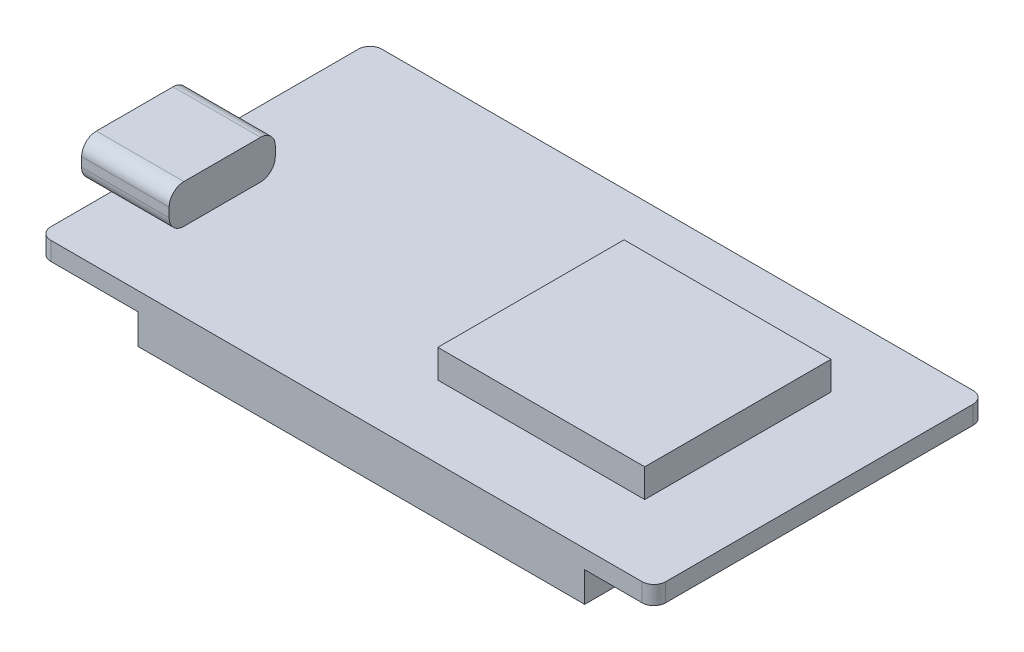
SolidWorks part; units mm, degrees
ref_plane "前基準面" through (0, 0, 0) normal (0, 0, 1) x (1, 0, 0)
ref_plane "上基準面" through (0, 0, 0) normal (0, 1, 0) x (1, 0, 0)
ref_plane "右基準面" through (0, 0, 0) normal (1, 0, 0) x (0, 0, -1)
sketch "草圖1" plane through (0, 0, 0) normal (0, 1, 0) x (1, 0, 0)
  line L1 (-26, 14) -> (26, 14)
  line L2 (-26, 14) -> (-26, -14)
  line L3 (-26, -14) -> (26, -14)
  line L4 (26, 14) -> (26, -14)
  line L5 (-26, 14) -> (26, -14) construction
  line L6 (-26, -14) -> (26, 14) construction
  point P0 (0, 0)
  dimension "D1" = 28
  dimension "D2" = 52
extrude "填料-伸長1" add sketch "草圖1" along normal blind 1.55
fillet "圓角1" radius 1 4 edges at (26, 0.775, -14) (-26, 0.775, -14) (-26, 0.775, 14) (26, 0.775, 14)
sketch "草圖2" plane through (0, 0, 0) normal (0, -1, 0) x (1, 0, 0)
  line L0 (-25, 14) -> (25, 14) construction
  line L1 (-17.61, 14) -> (20.15, 14)
  line L2 (-17.61, 14) -> (-17.61, 11.46)
  line L3 (-17.61, 11.46) -> (20.15, 11.46)
  line L4 (20.15, 14) -> (20.15, 11.46)
  line L5 (26, 13) -> (26, -13) construction
  line L6 (-26, 0) -> (26, 0) construction
  line L7 (-26, -13) -> (-26, 13) construction
  line L8 (20.15, -14) -> (20.15, -11.46)
  line L9 (-17.61, -14) -> (-17.61, -11.46)
  line L10 (-17.61, -14) -> (20.15, -14)
  line L11 (-17.61, -11.46) -> (20.15, -11.46)
  dimension "D1" = 2.54
  dimension "D2" = 37.76
  dimension "D3" = 5.85
extrude "填料-伸長2" add sketch "草圖2" along normal blind 2.54
sketch "草圖3" plane through (0, 1.55, 0) normal (0, 1, 0) x (1, 0, 0)
  line L0 (26, -13) -> (26, 13) construction
  line L1 (1.6, 7.875) -> (19.1, 7.875)
  line L2 (1.6, 7.875) -> (1.6, -7.875)
  line L3 (1.6, -7.875) -> (19.1, -7.875)
  line L4 (19.1, 7.875) -> (19.1, -7.875)
  line L5 (1.6, 7.875) -> (19.1, -7.875) construction
  line L6 (1.6, -7.875) -> (19.1, 7.875) construction
  point P0 (10.35, 0)
  dimension "D1" = 17.5
  dimension "D2" = 15.75
  dimension "D3" = 6.9
extrude "填料-伸長4" add sketch "草圖3" along normal blind 2.4
sketch "草圖5" plane through (-26, 0, 0) normal (-1, 0, 0) x (0, 0, 1)
  line L0 (-13, 1.55) -> (13, 1.55) construction
  line L1 (7.35, 1.55) -> (0.87, 1.55)
  line L2 (8.6, 2.8) -> (8.6, 3.58)
  line L3 (7.35, 4.83) -> (0.87, 4.83)
  line L4 (-0.38, 2.8) -> (-0.38, 3.58)
  line L5 (-7.875, 1.55) -> (7.875, 1.55) construction
  line L6 (14, 1.55) -> (14, 0) construction
  line L7 (-0.38, 3.19) -> (8.6, 3.19) construction
  line L8 (4.11, 4.83) -> (4.11, 1.55) construction
  arc A0 (0.87, 4.83) -> (-0.38, 3.58) centre (0.87, 3.58) ccw
  arc A1 (0.87, 1.55) -> (-0.38, 2.8) centre (0.87, 2.8) cw
  arc A2 (7.35, 1.55) -> (8.6, 2.8) centre (7.35, 2.8) ccw
  arc A3 (8.6, 3.58) -> (7.35, 4.83) centre (7.35, 3.58) ccw
  point P13 (-0.38, 4.83)
  point P16 (-0.38, 1.55)
  point P19 (8.6, 1.55)
  point P22 (8.6, 4.83)
  point P26 (4.11, 3.19)
  point P27 (4.11, 3.19)
  point P28 (4.11, 3.19)
  dimension "D4" = 1.25
  dimension "D1" = 3.28
  dimension "D2" = 8.98
  dimension "D3" = 5.4
extrude "填料-伸長6" add sketch "草圖5" against normal blind 5.6 and the other way blind 1.8
